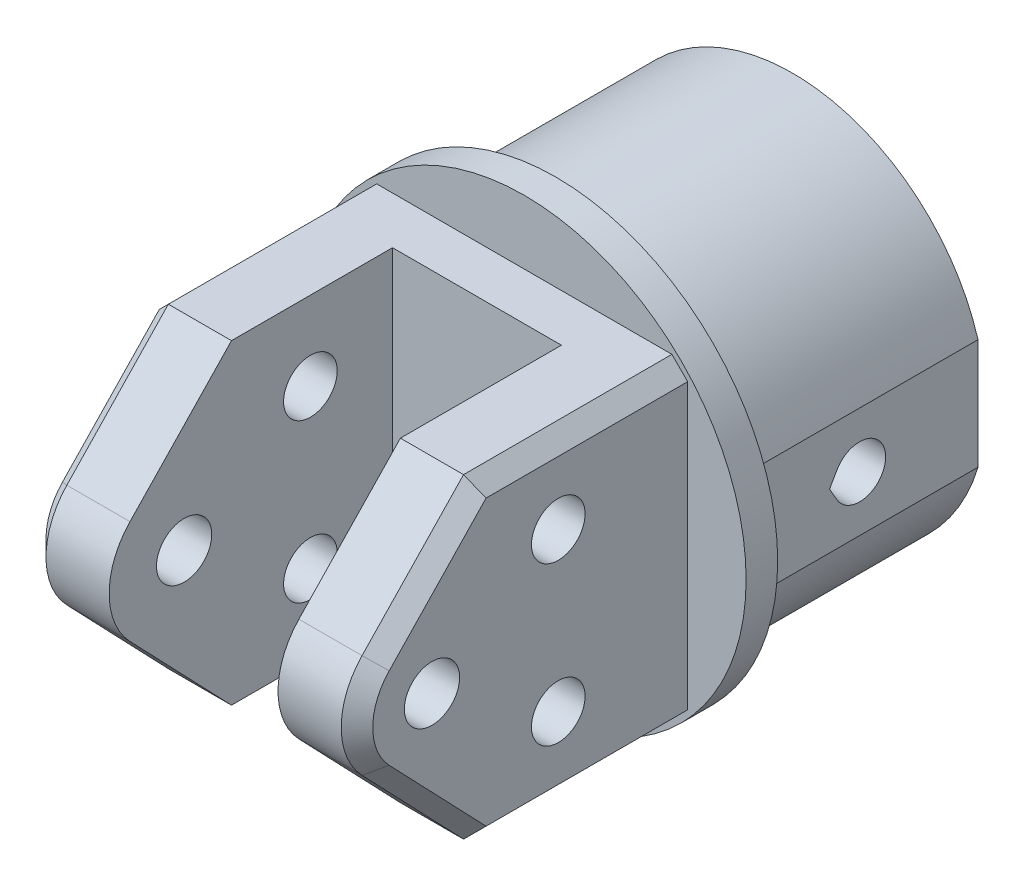
SolidWorks part; units mm, degrees
ref_plane "正面(Front)" through (0, 0, 0) normal (0, 0, 1) x (1, 0, 0)
ref_plane "平面(Top)" through (0, 0, 0) normal (0, 1, 0) x (1, 0, 0)
ref_plane "右側面(Right)" through (0, 0, 0) normal (1, 0, 0) x (0, 0, -1)
sketch "ｽｹｯﾁ1" plane through (0, 0, 0) normal (0, 0, 1) x (1, 0, 0)
  circle A0 centre (0, 0) radius 6.325
  dimension "D1" = 12.65
extrude "ﾎﾞｽ - 押し出し1" add sketch "ｽｹｯﾁ1" against normal blind 15
sketch "ｽｹｯﾁ2" plane through (0, 0, 0) normal (0, 0, 1) x (1, 0, 0)
  line L1 (-10.35, 10) -> (10.35, 10)
  line L2 (-10.35, 10) -> (-10.35, -10)
  line L3 (-10.35, -10) -> (10.35, -10)
  line L4 (10.35, 10) -> (10.35, -10)
  line L5 (-10.35, 10) -> (10.35, -10) construction
  line L6 (-10.35, -10) -> (10.35, 10) construction
  point P0 (0, 0)
  dimension "D1" = 20.7
  dimension "D2" = 20
extrude "ﾎﾞｽ - 押し出し2" add sketch "ｽｹｯﾁ2" along normal blind 5
sketch "ｽｹｯﾁ3" plane through (0, 0, 5) normal (0, 0, 1) x (1, 0, 0)
  line L0 (-10.35, -10) -> (10.35, -10) construction
  line L1 (10.35, 10) -> (5.35, 10)
  line L2 (10.35, 10) -> (10.35, -10)
  line L3 (10.35, -10) -> (5.35, -10)
  line L4 (5.35, 10) -> (5.35, -10)
  line L6 (-10.35, 10) -> (-5.35, 10)
  line L7 (-10.35, 10) -> (-10.35, -10)
  line L8 (-10.35, -10) -> (-5.35, -10)
  line L9 (-5.35, 10) -> (-5.35, -10)
  dimension "D1" = 5
extrude "ﾎﾞｽ - 押し出し3" add sketch "ｽｹｯﾁ3" along normal blind 10.2
fillet "ﾌｨﾚｯﾄ1" [suppressed] radius 5
sketch "ｽｹｯﾁ4" plane through (0, 0, 0) normal (1, 0, 0) x (0, 0, -1)
  line L0 (0, 0) -> (-25.6063, 0) construction
  line L2 (-15.2, -10) -> (-15.2, 10) construction
  circle A0 centre (-10.2, 5) radius 1.7
  circle A1 centre (-10.2, -5) radius 1.7
  dimension "D1" = 3.4
  dimension "D2" = 5
  dimension "D3" = 5
extrude "ｶｯﾄ - 押し出し1" cut sketch "ｽｹｯﾁ4" against normal through all both and the other way through all
sketch "ｽｹｯﾁ5" plane through (0, 0, 0) normal (1, 0, 0) x (0, 0, -1)
  line L0 (0, 0) -> (17.4374, 0) construction
  line L1 (0, -10) -> (0, 10) construction
  circle A0 centre (7.5, 0) radius 1.65
  dimension "D1" = 7.5
  dimension "D2" = 3.3
extrude "ｶｯﾄ - 押し出し2" cut sketch "ｽｹｯﾁ5" against normal through all both and the other way through all
sketch "ｽｹｯﾁ6" plane through (-10.35, 0, 0) normal (-1, 0, 0) x (0, 0, 1)
  line L0 (15.2, 10) -> (21.6305, 3.2854)
  line L1 (0, 0) -> (33.6489, 0) construction
  line L2 (15.2, -10) -> (21.6305, -3.2854)
  line L3 (15.2, -10) -> (15.2, 10)
  arc A0 (21.6305, 3.2854) -> (21.6305, -3.2854) centre (18.2, 0) cw
  circle A1 centre (18.2, 0) radius 1.75
  circle A2 centre (10.2, 5) radius 1.7 construction
  dimension "D1" = 3.5
  dimension "D2" = 8
  dimension "D3" = 3
extrude "ﾎﾞｽ - 押し出し4" add sketch "ｽｹｯﾁ6" against normal blind 5
fillet "ﾌｨﾚｯﾄ2" [suppressed] radius 10
mirror "ﾐﾗｰ1" about plane through (0, 0, 0) normal (1, 0, 0) of "ﾎﾞｽ - 押し出し4", "ﾌｨﾚｯﾄ2"
chamfer "面取り1" [suppressed] distance 1 angle 45
chamfer "面取り2" distance 1 angle 45 10 edges at (10.35, 10, 7.6) (10.35, -10, 7.6) (-10.35, 10, 7.6) (-10.35, -10, 7.6) (10.35, 6.6427, 18.4153) (10.35, 0, 22.95) (10.35, -6.6427, 18.4153) (-10.35, 6.6427, 18.4153) (-10.35, 0, 22.95) (-10.35, -6.6427, 18.4153)
chamfer "面取り3" distance 1 angle 45 1 edges at (6.325, 0, -15)
sketch "ｽｹｯﾁ8" plane through (0, 10, 0) normal (0, 1, 0) x (1, 0, 0)
  line L0 (-16.3251, 0) -> (21.4444, 0)
extrude "ｶｯﾄ - 押し出し3" cut sketch "ｽｹｯﾁ8" against normal through all and the other way through all
sketch "ｽｹｯﾁ9" plane through (0, 0, 0) normal (0, 0, -1) x (-1, 0, 0)
  circle A0 centre (0, 0) radius 9.25
  circle A1 centre (0, 0) radius 12.25
  dimension "D1" = 18.5
  dimension "D2" = 3
extrude "ﾎﾞｽ - 押し出し5" add sketch "ｽｹｯﾁ9" along normal blind 15
sketch "ｽｹｯﾁ10" plane through (0, 0, 0) normal (0, 0, 1) x (1, 0, 0)
  circle A0 centre (0, 0) radius 14.05
  arc A1 (10.35, -6.5529) -> (10.35, 6.5529) centre (0, 0) ccw construction
  dimension "D1" = 1.8
extrude "ﾎﾞｽ - 押し出し6" add sketch "ｽｹｯﾁ10" along normal blind 2
sketch "ｽｹｯﾁ11" plane through (0, 0, 0) normal (1, 0, 0) x (0, 0, -1)
  line L0 (0, -14.05) -> (0, 14.05) construction
  line L1 (0, 0) -> (20.2478, 0) construction
  line L2 (6.0711, 0.825) -> (5.5947, 0)
  line L3 (5.5947, 0) -> (6.0711, -0.825)
  arc A0 (6.0711, -0.825) -> (6.0711, 0.825) centre (7.5, 0) ccw
  dimension "D1" = 7.5
  dimension "D2" = 3.3
  dimension "D3" = 60
extrude "ｶｯﾄ - 押し出し4" cut sketch "ｽｹｯﾁ11" against normal through all both and the other way through all
sketch "ｽｹｯﾁ12" plane through (0, 0, -15) normal (0, 0, -1) x (-1, 0, 0)
  line L0 (-11.7394, 3.5) -> (-11.7394, -3.5)
  line L1 (0, 0) -> (0, 22.0096) construction
  line L2 (11.7394, 3.5) -> (11.7394, -3.5)
  line L3 (-11.7394, 3.5) -> (-16.1799, 3.5)
  line L4 (-16.1799, 3.5) -> (-16.1799, -3.5)
  line L5 (-16.1799, -3.5) -> (-11.7394, -3.5)
  line L6 (11.7394, -3.5) -> (17.2092, -3.5)
  line L7 (17.2092, -3.5) -> (17.2092, 3.5)
  line L8 (17.2092, 3.5) -> (11.7394, 3.5)
  circle A0 centre (0, 0) radius 12.25 construction
  dimension "D1" = 7
extrude "ｶｯﾄ - 押し出し5" cut sketch "ｽｹｯﾁ12" against normal up to surface (15 mm away) up to face at (-12.25, 0, 0)
